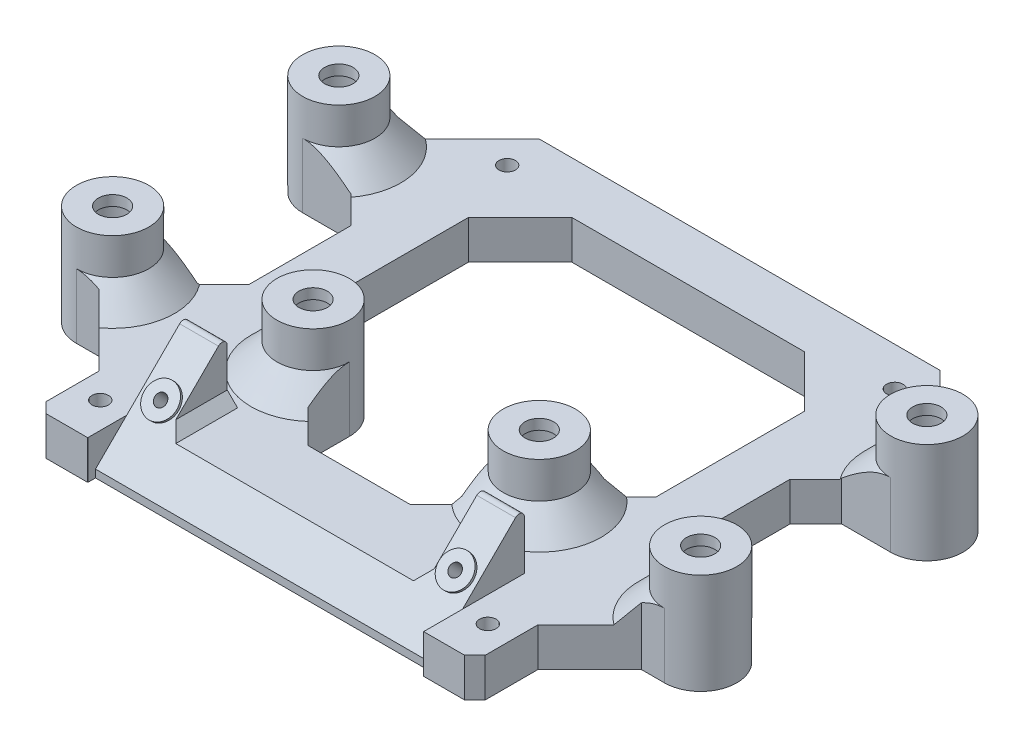
SolidWorks part; units mm, degrees
ref_plane "正面" through (0, 0, 0) normal (0, 0, 1) x (1, 0, 0)
ref_plane "平面" through (0, 0, 0) normal (0, 1, 0) x (1, 0, 0)
ref_plane "右側面" through (0, 0, 0) normal (1, 0, 0) x (0, 0, -1)
sketch "ｽｹｯﾁ1" plane through (0, 0, 0) normal (0, 1, 0) x (1, 0, 0)
  line L0 (42.4208, -126.095) -> (42.4208, 32.495) construction
  line L1 (42.4208, 32.495) -> (32.4208, 32.495) construction
  line L2 (32.4208, 32.495) -> (32.4208, -126.095) construction
  line L3 (32.4208, -126.095) -> (42.4208, -126.095) construction
  line L4 (-32.5792, -126.1) -> (-32.5792, 32.49) construction
  line L5 (-32.5792, 32.49) -> (-42.5792, 32.49) construction
  line L6 (-42.5792, 32.49) -> (-42.5792, -126.1) construction
  line L7 (-42.5792, -126.1) -> (-32.5792, -126.1) construction
  line L8 (42.4208, -126.095) -> (42.4208, -113.8873)
  line L9 (42.4208, 32.495) -> (32.4208, 32.495)
  line L10 (32.4208, -116.095) -> (32.4208, -126.095)
  line L11 (32.4208, -126.095) -> (42.4208, -126.095)
  line L12 (-32.5792, -126.1) -> (-32.5792, -116.095)
  line L13 (-32.5792, 32.49) -> (-42.5792, 32.49)
  line L14 (-42.5792, 32.49) -> (-42.5792, -36.1127)
  line L15 (-42.5792, -126.1) -> (-32.5792, -126.1)
  line L16 (42.4208, -36.1127) -> (42.4208, 32.495)
  line L17 (42.4208, 32.495) -> (32.4208, 32.495)
  line L18 (32.4208, -52.345) -> (32.4208, -126.095)
  line L19 (32.4208, -126.095) -> (42.4208, -126.095)
  line L20 (-32.5792, -126.1) -> (-32.5792, -52.345)
  line L21 (-32.5792, 32.49) -> (-42.5792, 32.49)
  line L22 (-42.5792, -113.8873) -> (-42.5792, -126.1)
  line L23 (-42.5792, -126.1) -> (-32.5792, -126.1)
  line L24 (0, 0) -> (0, -126.0975) construction
  line L25 (-14.8873, -93.1) -> (-14.8873, -106.095)
  line L26 (-32.5792, -126.1) -> (32.4208, -126.095) construction
  line L27 (-56.9, -89.8873) -> (-42.5792, -89.8873)
  line L28 (-56.9, -103.8873) -> (-52.5792, -103.8873)
  line L29 (-56.9, -60.1127) -> (-42.5792, -60.1127)
  line L30 (-56.9, -46.1127) -> (-52.5792, -46.1127)
  line L31 (14.8873, -93.1) -> (14.8873, -106.095)
  line L32 (-21.8873, -86.1) -> (-32.5792, -86.1)
  line L34 (21.8873, -86.1) -> (32.5792, -86.1)
  line L35 (56.9, -46.1127) -> (52.4208, -46.1127)
  line L36 (56.9, -60.1127) -> (42.5792, -60.1127)
  line L37 (56.9, -103.8873) -> (52.4208, -103.8873)
  line L38 (56.9, -89.8873) -> (42.5792, -89.8873)
  line L39 (-38.8115, -32.345) -> (38.6531, -32.345)
  line L40 (-42.5792, -36.1127) -> (-52.5792, -46.1127)
  line L41 (-52.5792, -103.8873) -> (-42.5792, -113.8873)
  line L42 (52.4208, -103.8873) -> (42.4208, -113.8873)
  line L43 (52.4208, -46.1127) -> (42.4208, -36.1127)
  line L45 (-32.5792, -106.095) -> (32.4208, -106.095)
  line L46 (-22.5792, -42.345) -> (22.4208, -42.345)
  line L47 (-32.5792, -52.345) -> (-22.5792, -42.345)
  line L48 (42.4208, -126.095) -> (42.4208, 32.495)
  line L49 (42.4208, 32.495) -> (32.4208, 32.495)
  line L50 (32.4208, 32.495) -> (32.4208, -126.095)
  line L51 (32.4208, -126.095) -> (42.4208, -126.095)
  line L52 (42.4208, -126.095) -> (42.4208, 32.495)
  line L53 (42.4208, 32.495) -> (32.4208, 32.495)
  line L54 (32.4208, 32.495) -> (32.4208, -126.095)
  line L55 (32.4208, -126.095) -> (42.4208, -126.095)
  line L56 (22.4208, -42.345) -> (32.4208, -52.345)
  line L57 (42.5792, -60.1127) -> (42.4208, -60.1127)
  line L58 (42.5792, -89.8873) -> (42.4208, -89.8873)
  line L59 (-42.5792, -36.1127) -> (-38.8115, -32.345)
  line L60 (42.4208, -36.1127) -> (38.6531, -32.345)
  line L61 (-32.5792, -126.1) -> (-32.5792, 32.49)
  line L62 (-32.5792, 32.49) -> (-42.5792, 32.49)
  line L63 (-42.5792, 32.49) -> (-42.5792, -126.1)
  line L64 (-42.5792, -126.1) -> (-32.5792, -126.1)
  line L65 (-32.5792, -126.1) -> (-32.5792, 32.49)
  line L66 (-32.5792, 32.49) -> (-42.5792, 32.49)
  line L67 (-42.5792, 32.49) -> (-42.5792, -126.1)
  line L68 (-42.5792, -126.1) -> (-32.5792, -126.1)
  line L69 (-32.5792, -106.095) -> (-32.5792, -116.095)
  line L70 (-32.5792, -116.095) -> (32.4208, -116.095)
  line L71 (32.4208, -106.095) -> (32.4208, -116.095)
  circle A0 centre (-21.8873, -93.1) radius 2.5 construction
  circle A1 centre (37.5, -27.5) radius 1.6
  circle A2 centre (37.5, -27.5) radius 1.6
  circle A3 centre (37.5, 27.5) radius 1.6
  circle A4 centre (37.5, 27.5) radius 1.6
  circle A5 centre (37.4208, -39.845) radius 1.6
  circle A6 centre (37.4208, -39.845) radius 1.6
  circle A7 centre (37.4208, -118.595) radius 1.6
  circle A8 centre (37.4208, -118.595) radius 1.6
  circle A9 centre (-37.5, -27.505) radius 1.6
  circle A10 centre (-37.5, -27.505) radius 1.6
  circle A11 centre (-37.5, 27.495) radius 1.6
  circle A12 centre (-37.5, 27.495) radius 1.6
  circle A13 centre (-37.5792, -39.85) radius 1.6
  circle A14 centre (-37.5792, -39.85) radius 1.6
  circle A15 centre (-37.5792, -118.6) radius 1.6
  circle A16 centre (-37.5792, -118.6) radius 1.6
  circle A17 centre (21.8873, -93.1) radius 2.5 construction
  circle A18 centre (56.9, -96.8873) radius 2.5 construction
  circle A19 centre (56.9, -53.1127) radius 2.5 construction
  circle A20 centre (-56.9, -96.8873) radius 2.5 construction
  circle A21 centre (-56.9, -53.1127) radius 2.5 construction
  circle A22 centre (-21.8873, -93.1) radius 2.5
  circle A23 centre (21.8873, -93.1) radius 2.5
  circle A24 centre (56.9, -96.8873) radius 2.5
  circle A25 centre (56.9, -53.1127) radius 2.5
  circle A26 centre (-56.9, -96.8873) radius 2.5
  circle A27 centre (-56.9, -53.1127) radius 2.5
  circle A28 centre (-21.8873, -93.1) radius 7
  circle A30 centre (-56.9, -53.1127) radius 7
  circle A31 centre (-56.9, -96.8873) radius 7
  circle A32 centre (21.8873, -93.1) radius 2.5
  circle A33 centre (21.8873, -93.1) radius 7
  circle A34 centre (56.9, -96.8873) radius 7
  circle A35 centre (56.9, -53.1127) radius 7
  circle A36 centre (56.9, -53.1127) radius 2.5
  circle A37 centre (56.9, -96.8873) radius 2.5
  point P62 (-42.5792, -103.8873)
  point P66 (-42.5792, -46.1127)
  point P97 (42.4208, -103.8873)
  point P99 (42.4208, -46.1127)
  point P110 (-32.5792, -42.345)
  point P111 (32.4208, -42.345)
  dimension "D9" = 14
  dimension "D10" = 14
  dimension "D21" = 14
  dimension "D11" = 7.5
  dimension "D20" = 10
  dimension "D19" = 10
  dimension "D13" = 10
  dimension "D1" = 0
  dimension "D2" = 0
  dimension "D3" = 0
  dimension "D4" = 0
  dimension "D5" = 0
  dimension "D6" = 0
  dimension "D7" = 0
  dimension "D8" = 0
  dimension "D12" = 0
  dimension "D18" = 0
extrude "ﾎﾞｽ - 押し出し1" add sketch "ｽｹｯﾁ1" along normal blind 7.5 contours A30 L29 L67 L40 L30 | A31 L28 L41 L67 L27 | L14 L67 L22 L15 L12 L20 L65 L39 A16 A14 | L39 L54 L18 L10 L11 L8 L52 L16 A8 A6 | L34 A33 L18 | A28 L32 L20 | A28 A22 | A31 A26 | A30 A27 | A35 A25 | L36 A35 L35 L43 L52 L57 | L65 L47 L46 L56 L54 L39 | L37 A34 L38 L58 L52 L42 | A34 A24 | A33 A23 | L20 L70 L18 L45 region at (37.3917, 0, 79.5741) region at (46.6794, 0, 99.8273) region at (-0.0792, 0, 111.095) region at (50.098, 0, 96.8873) region at (46.6794, 0, 50.1727) region at (23.654, 0, 105.8291) region at (-37.5502, 0, 79.5766) region at (-32.3122, 0, 96.0975) region at (50.098, 0, 53.1127) region at (-0.0792, 0, 38.4561) region at (26.697, 0, 88.2903) region at (-26.697, 0, 97.9097) region at (-46.7785, 0, 99.8648) region at (-63.702, 0, 96.8873) region at (-46.7785, 0, 50.1352) region at (-63.702, 0, 53.1127)
chamfer "面取り1" distance 10 angle 45 2 edges at (32.4208, 3.75, 116.095) (-32.5792, 3.75, 116.095)
chamfer "面取り2" distance 5 angle 45 2 edges at (14.8873, 3.75, 106.095) (-14.8873, 3.75, 106.095)
chamfer "面取り3" distance 5 angle 45 6 edges at (42.4208, 3.75, 89.8873) (42.4208, 3.75, 60.1127) (-42.5792, 3.75, 89.8873) (-42.5792, 3.75, 60.1127) (32.4208, 3.75, 86.1) (-32.5792, 3.75, 86.1)
chamfer "面取り4" distance 2 angle 45 2 edges at (42.4208, 3.75, 126.095) (-42.5792, 3.75, 126.1)
sketch "ｽｹｯﾁ2" plane through (0, 7.5, 0) normal (0, 1, 0) x (1, 0, 0)
  circle A0 centre (-56.9, -53.1127) radius 5.1
  circle A1 centre (-56.9, -96.8873) radius 5.1
  circle A2 centre (56.9, -53.1127) radius 5.1
  circle A3 centre (56.9, -96.8873) radius 5.1
  circle A4 centre (21.8873, -93.1) radius 5.1
  circle A5 centre (-21.8873, -93.1) radius 5.1
  dimension "D1" = 10.2
  dimension "D2" = 10.2
  dimension "D3" = 10.2
  dimension "D4" = 10.2
  dimension "D5" = 10.2
  dimension "D6" = 10.2
extrude "ｶｯﾄ - 押し出し1" cut sketch "ｽｹｯﾁ2" against normal blind 7.5
sketch "ｽｹｯﾁ3" plane through (0, 7.5, 0) normal (0, 1, 0) x (1, 0, 0)
  circle A0 centre (56.9, -96.8873) radius 5.1 construction
  circle A1 centre (21.8873, -93.1) radius 5.1 construction
  circle A2 centre (-21.8873, -93.1) radius 5.1 construction
  circle A3 centre (-56.9, -96.8873) radius 5.1 construction
  circle A4 centre (-56.9, -53.1127) radius 5.1 construction
  circle A5 centre (56.9, -53.1127) radius 5.1 construction
  circle A6 centre (56.9, -96.8873) radius 5.1
  circle A7 centre (21.8873, -93.1) radius 5.1
  circle A8 centre (-21.8873, -93.1) radius 5.1
  circle A9 centre (-56.9, -96.8873) radius 5.1
  circle A10 centre (-56.9, -53.1127) radius 5.1
  circle A11 centre (56.9, -53.1127) radius 5.1
  circle A12 centre (-56.9, -53.1127) radius 7
  circle A13 centre (-56.9, -96.8873) radius 7
  circle A14 centre (56.9, -53.1127) radius 7
  circle A15 centre (56.9, -96.8873) radius 7
  circle A16 centre (21.8873, -93.1) radius 7
  circle A17 centre (-21.8873, -93.1) radius 7
  dimension "D1" = 14
  dimension "D2" = 14
  dimension "D3" = 14
  dimension "D4" = 14
  dimension "D5" = 14
  dimension "D6" = 14
extrude "ﾎﾞｽ - 押し出し2" add sketch "ｽｹｯﾁ3" along normal blind 10
sketch "ｽｹｯﾁ4" plane through (0, 17.5, 0) normal (0, 1, 0) x (1, 0, 0)
  circle A0 centre (56.9, -53.1127) radius 7 construction
  circle A1 centre (56.9, -96.8873) radius 7 construction
  circle A2 centre (21.8873, -93.1) radius 7 construction
  circle A3 centre (-21.8873, -93.1) radius 7 construction
  circle A4 centre (-56.9, -96.8873) radius 7 construction
  circle A5 centre (-56.9, -53.1127) radius 7 construction
  circle A6 centre (56.9, -53.1127) radius 7
  circle A7 centre (56.9, -96.8873) radius 7
  circle A8 centre (21.8873, -93.1) radius 7
  circle A9 centre (-21.8873, -93.1) radius 7
  circle A10 centre (-56.9, -96.8873) radius 7
  circle A11 centre (-56.9, -53.1127) radius 7
  circle A12 centre (-56.9, -53.1127) radius 2.75
  circle A13 centre (-56.9, -96.8873) radius 2.75
  circle A14 centre (-21.8873, -93.1) radius 2.75
  circle A15 centre (21.8873, -93.1) radius 2.75
  circle A16 centre (56.9, -53.1127) radius 2.75
  circle A17 centre (56.9, -96.8873) radius 2.75
  dimension "D1" = 5.5
  dimension "D2" = 5.5
  dimension "D3" = 5.5
  dimension "D4" = 5.5
  dimension "D5" = 5.5
  dimension "D6" = 5.5
extrude "ﾎﾞｽ - 押し出し3" add sketch "ｽｹｯﾁ4" along normal blind 2
chamfer "面取り5" distance 5 angle 45 6 edges at (49.9, 7.5, 53.1127) (49.9, 7.5, 96.8873) (26.837, 7.5, 98.0497) (-26.837, 7.5, 98.0497) (-49.9, 7.5, 96.8873) (-49.9, 7.5, 53.1127)
sketch "ｽｹｯﾁ5" plane through (0, 0, 0) normal (0, -1, 0) x (1, 0, 0)
  line L0 (-56.9, 96.8873) -> (-46.9, 96.8873) construction
  line L1 (-56.9, 99.9873) -> (-46.9, 99.9873)
  line L2 (-56.9, 93.7873) -> (-46.9, 93.7873)
  line L3 (-56.9, 53.1127) -> (-46.9, 53.1127) construction
  line L4 (-56.9, 56.2127) -> (-46.9, 56.2127)
  line L5 (-56.9, 50.0127) -> (-46.9, 50.0127)
  line L6 (-21.8873, 93.1) -> (-28.9584, 100.1711) construction
  line L7 (-24.0793, 90.908) -> (-31.1504, 97.979)
  line L8 (-19.6953, 95.292) -> (-26.7663, 102.3631)
  line L9 (21.8873, 93.1) -> (28.9584, 100.1711) construction
  line L10 (19.6953, 95.292) -> (26.7663, 102.3631)
  line L11 (24.0793, 90.908) -> (31.1504, 97.979)
  line L12 (56.9, 96.8873) -> (46.9, 96.8873) construction
  line L13 (56.9, 93.7873) -> (46.9, 93.7873)
  line L14 (22.4208, 42.345) -> (32.4208, 52.345)
  line L15 (-22.5792, 42.345) -> (22.4208, 42.345)
  line L16 (-32.5792, 52.345) -> (-22.5792, 42.345)
  line L17 (-32.5792, 81.1) -> (-32.5792, 52.345)
  line L18 (-27.5792, 86.1) -> (-32.5792, 81.1)
  line L19 (-21.8873, 86.1) -> (-27.5792, 86.1)
  line L20 (-14.8873, 101.095) -> (-14.8873, 93.1)
  line L21 (-9.8873, 106.095) -> (-14.8873, 101.095)
  line L22 (9.8873, 106.095) -> (-9.8873, 106.095)
  line L23 (14.8873, 101.095) -> (9.8873, 106.095)
  line L24 (14.8873, 93.1) -> (14.8873, 101.095)
  line L25 (27.4208, 86.1) -> (21.8873, 86.1)
  line L26 (32.4208, 81.1) -> (27.4208, 86.1)
  line L27 (32.4208, 52.345) -> (32.4208, 81.1)
  line L28 (22.4208, 42.345) -> (32.4208, 52.345)
  line L29 (-22.5792, 42.345) -> (22.4208, 42.345)
  line L30 (-32.5792, 52.345) -> (-22.5792, 42.345)
  line L31 (-32.5792, 81.1) -> (-32.5792, 52.345)
  line L32 (-27.5792, 86.1) -> (-32.5792, 81.1)
  line L33 (-21.8873, 86.1) -> (-27.5792, 86.1)
  line L34 (-14.8873, 101.095) -> (-14.8873, 93.1)
  line L35 (-9.8873, 106.095) -> (-14.8873, 101.095)
  line L36 (9.8873, 106.095) -> (-9.8873, 106.095)
  line L37 (14.8873, 101.095) -> (9.8873, 106.095)
  line L38 (14.8873, 93.1) -> (14.8873, 101.095)
  line L39 (27.4208, 86.1) -> (21.8873, 86.1)
  line L40 (32.4208, 81.1) -> (27.4208, 86.1)
  line L41 (32.4208, 52.345) -> (32.4208, 81.1)
  line L42 (56.9, 99.9873) -> (46.9, 99.9873)
  line L43 (56.9, 53.1127) -> (46.9, 53.1127) construction
  line L44 (56.9, 50.0127) -> (46.9, 50.0127)
  line L45 (56.9, 56.2127) -> (46.9, 56.2127)
  arc A0 (-56.9, 99.9873) -> (-56.9, 93.7873) centre (-56.9, 96.8873) ccw
  circle A1 centre (-37.5792, 118.6) radius 1.6
  arc A2 (-21.8873, 86.1) -> (-14.8873, 93.1) centre (-21.8873, 93.1) ccw
  arc A3 (14.8873, 93.1) -> (21.8873, 86.1) centre (21.8873, 93.1) ccw
  arc A4 (-21.8873, 86.1) -> (-14.8873, 93.1) centre (-21.8873, 93.1) ccw
  arc A5 (14.8873, 93.1) -> (21.8873, 86.1) centre (21.8873, 93.1) ccw
  circle A6 centre (-37.5792, 118.6) radius 1.6
  circle A7 centre (-37.5792, 39.85) radius 1.6
  circle A8 centre (-37.5792, 39.85) radius 1.6
  circle A9 centre (37.4208, 118.595) radius 1.6
  circle A10 centre (37.4208, 118.595) radius 1.6
  circle A11 centre (37.4208, 39.845) radius 1.6
  circle A12 centre (37.4208, 39.845) radius 1.6
  circle A13 centre (-56.9, 53.1127) radius 5.1
  circle A14 centre (-56.9, 53.1127) radius 5.1
  circle A15 centre (-21.8873, 93.1) radius 5.1
  circle A16 centre (-21.8873, 93.1) radius 5.1
  circle A17 centre (-56.9, 96.8873) radius 5.1
  circle A18 centre (-56.9, 96.8873) radius 5.1
  circle A19 centre (56.9, 53.1127) radius 5.1
  circle A20 centre (56.9, 53.1127) radius 5.1
  circle A21 centre (56.9, 96.8873) radius 5.1
  circle A22 centre (56.9, 96.8873) radius 5.1
  circle A23 centre (21.8873, 93.1) radius 5.1
  circle A24 centre (21.8873, 93.1) radius 5.1
  arc A25 (-46.9, 93.7873) -> (-46.9, 99.9873) centre (-46.9, 96.8873) ccw
  circle A26 centre (-46.9, 96.8873) radius 1.4
  arc A27 (-56.9, 56.2127) -> (-56.9, 50.0127) centre (-56.9, 53.1127) ccw
  arc A28 (-46.9, 50.0127) -> (-46.9, 56.2127) centre (-46.9, 53.1127) ccw
  circle A29 centre (-46.9, 53.1127) radius 1.4
  arc A30 (-24.0793, 90.908) -> (-19.6953, 95.292) centre (-21.8873, 93.1) ccw
  arc A31 (-26.7663, 102.3631) -> (-31.1504, 97.979) centre (-28.9584, 100.1711) ccw
  arc A32 (19.6953, 95.292) -> (24.0793, 90.908) centre (21.8873, 93.1) ccw
  arc A33 (31.1504, 97.979) -> (26.7663, 102.3631) centre (28.9584, 100.1711) ccw
  arc A34 (56.9, 93.7873) -> (56.9, 99.9873) centre (56.9, 96.8873) ccw
  arc A35 (46.9, 99.9873) -> (46.9, 93.7873) centre (46.9, 96.8873) ccw
  arc A36 (56.9, 50.0127) -> (56.9, 56.2127) centre (56.9, 53.1127) ccw
  arc A37 (46.9, 56.2127) -> (46.9, 50.0127) centre (46.9, 53.1127) ccw
  circle A39 centre (-28.9584, 100.1711) radius 1.4
  circle A40 centre (28.9584, 100.1711) radius 1.4
  circle A41 centre (46.9, 96.8873) radius 1.4
  circle A42 centre (46.9, 53.1127) radius 1.4
  point P6 (-51.9, 96.8873)
  point P56 (-51.9, 53.1127)
  point P64 (-25.4228, 96.6355)
  point P70 (25.4228, 96.6355)
  point P76 (51.9, 96.8873)
  point P82 (51.9, 53.1127)
  dimension "D14" = 2.8
  dimension "D16" = 3.1
  dimension "D17" = 2.8
  dimension "D19" = 3.1
  dimension "D21" = 3.1
  dimension "D24" = 3.1
  dimension "D26" = 3.1
  dimension "D27" = 2.8
  dimension "D28" = 2.8
  dimension "D29" = 2.8
  dimension "D30" = 2.8
  dimension "D12" = 10
  dimension "D13" = 6.2
  dimension "D15" = 10
  dimension "D18" = 10
  dimension "D20" = 45
  dimension "D22" = 10
  dimension "D23" = 10
  dimension "D25" = 10
  dimension "D1" = 0
  dimension "D2" = 0
  dimension "D3" = 0
  dimension "D4" = 0
  dimension "D5" = 0
  dimension "D6" = 0
  dimension "D7" = 0
  dimension "D8" = 0
  dimension "D9" = 0
  dimension "D10" = 0
  dimension "D11" = 0
extrude "ｶｯﾄ - 押し出し2" cut sketch "ｽｹｯﾁ5" against normal blind 2.5 contours L2 A25 L1 A18 A26 | A26 | L7 A30 L8 A16 | L8 A31 L7 A16 A39 | A29 | L5 A28 L4 A14 A29 | L45 A37 L44 A20 A42 | A42 | A40 | L11 A33 L10 A24 A40 | A41 | L42 A35 L13 A22 A41 | A39 region at (-48.4792, 0, 96.8873) region at (-48.4792, 0, 53.1127) region at (-22.6926, 0, 93.9053) region at (-27.8417, 0, 99.0544) region at (27.8417, 0, 99.0544) region at (48.4792, 0, 96.8873) region at (48.4792, 0, 53.1127) region at (-46.9, 0, 96.8873) region at (-46.9, 0, 53.1127) region at (28.9584, 0, 100.1711) region at (46.9, 0, 96.8873) region at (46.9, 0, 53.1127)
sketch "ｽｹｯﾁ6" plane through (0, 2.5, 0) normal (0, -1, 0) x (1, 0, 0)
  line L2 (-46.9, 56.2127) -> (-56.9, 56.2127)
  line L3 (-56.9, 50.0127) -> (-46.9, 50.0127)
  line L4 (-46.9, 56.2127) -> (-56.9, 56.2127)
  line L5 (-56.9, 50.0127) -> (-46.9, 50.0127)
  line L6 (-46.9, 99.9873) -> (-56.9, 99.9873)
  line L7 (-56.9, 93.7873) -> (-46.9, 93.7873)
  line L8 (-46.9, 99.9873) -> (-56.9, 99.9873)
  line L9 (-56.9, 93.7873) -> (-46.9, 93.7873)
  line L10 (26.7663, 102.3631) -> (19.6953, 95.292)
  line L11 (24.0793, 90.908) -> (31.1504, 97.979)
  line L12 (26.7663, 102.3631) -> (19.6953, 95.292)
  line L13 (24.0793, 90.908) -> (31.1504, 97.979)
  line L14 (-9.8873, 106.095) -> (-14.8873, 101.095)
  line L15 (9.8873, 106.095) -> (-9.8873, 106.095)
  line L16 (14.8873, 101.095) -> (9.8873, 106.095)
  line L17 (14.8873, 93.1) -> (14.8873, 101.095)
  line L18 (27.4208, 86.1) -> (21.8873, 86.1)
  line L19 (32.4208, 81.1) -> (27.4208, 86.1)
  line L20 (32.4208, 52.345) -> (32.4208, 81.1)
  line L21 (22.4208, 42.345) -> (32.4208, 52.345)
  line L22 (-22.5792, 42.345) -> (22.4208, 42.345)
  line L23 (-32.5792, 52.345) -> (-22.5792, 42.345)
  line L24 (-32.5792, 81.1) -> (-32.5792, 52.345)
  line L25 (-27.5792, 86.1) -> (-32.5792, 81.1)
  line L26 (-21.8873, 86.1) -> (-27.5792, 86.1)
  line L27 (-14.8873, 101.095) -> (-14.8873, 93.1)
  line L28 (-9.8873, 106.095) -> (-14.8873, 101.095)
  line L29 (9.8873, 106.095) -> (-9.8873, 106.095)
  line L30 (14.8873, 101.095) -> (9.8873, 106.095)
  line L31 (14.8873, 93.1) -> (14.8873, 101.095)
  line L32 (27.4208, 86.1) -> (21.8873, 86.1)
  line L33 (32.4208, 81.1) -> (27.4208, 86.1)
  line L34 (32.4208, 52.345) -> (32.4208, 81.1)
  line L35 (22.4208, 42.345) -> (32.4208, 52.345)
  line L36 (-22.5792, 42.345) -> (22.4208, 42.345)
  line L37 (-32.5792, 52.345) -> (-22.5792, 42.345)
  line L38 (-32.5792, 81.1) -> (-32.5792, 52.345)
  line L39 (-27.5792, 86.1) -> (-32.5792, 81.1)
  line L40 (-21.8873, 86.1) -> (-27.5792, 86.1)
  line L41 (-14.8873, 101.095) -> (-14.8873, 93.1)
  line L42 (-31.1504, 97.979) -> (-24.0793, 90.908)
  line L43 (-19.6953, 95.292) -> (-26.7663, 102.3631)
  line L44 (-31.1504, 97.979) -> (-24.0793, 90.908)
  line L45 (-19.6953, 95.292) -> (-26.7663, 102.3631)
  line L46 (46.9, 50.0127) -> (56.9, 50.0127)
  line L47 (56.9, 56.2127) -> (46.9, 56.2127)
  line L48 (46.9, 50.0127) -> (56.9, 50.0127)
  line L49 (56.9, 56.2127) -> (46.9, 56.2127)
  line L50 (56.9, 99.9873) -> (46.9, 99.9873)
  line L51 (46.9, 93.7873) -> (56.9, 93.7873)
  line L52 (56.9, 99.9873) -> (46.9, 99.9873)
  line L53 (46.9, 93.7873) -> (56.9, 93.7873)
  circle A1 centre (-37.5792, 118.6) radius 1.6
  circle A2 centre (-37.5792, 118.6) radius 1.6
  circle A3 centre (37.4208, 39.845) radius 1.6
  circle A4 centre (37.4208, 39.845) radius 1.6
  circle A5 centre (37.4208, 118.595) radius 1.6
  circle A6 centre (37.4208, 118.595) radius 1.6
  circle A7 centre (-37.5792, 39.85) radius 1.6
  circle A8 centre (-37.5792, 39.85) radius 1.6
  circle A9 centre (56.9, 96.8873) radius 5.1
  arc A10 (14.8873, 93.1) -> (21.8873, 86.1) centre (21.8873, 93.1) ccw
  arc A11 (-21.8873, 86.1) -> (-14.8873, 93.1) centre (-21.8873, 93.1) ccw
  arc A12 (14.8873, 93.1) -> (21.8873, 86.1) centre (21.8873, 93.1) ccw
  arc A13 (-21.8873, 86.1) -> (-14.8873, 93.1) centre (-21.8873, 93.1) ccw
  circle A14 centre (56.9, 96.8873) radius 5.1
  circle A15 centre (56.9, 53.1127) radius 5.1
  circle A16 centre (56.9, 53.1127) radius 5.1
  circle A17 centre (-56.9, 96.8873) radius 5.1
  circle A18 centre (-56.9, 96.8873) radius 5.1
  circle A19 centre (-21.8873, 93.1) radius 5.1
  circle A20 centre (-21.8873, 93.1) radius 5.1
  circle A21 centre (-56.9, 53.1127) radius 5.1
  circle A22 centre (-56.9, 53.1127) radius 5.1
  circle A23 centre (-46.9, 53.1127) radius 1.4
  circle A24 centre (-46.9, 53.1127) radius 1.4
  circle A25 centre (-46.9, 96.8873) radius 1.4
  circle A26 centre (-46.9, 96.8873) radius 1.4
  circle A27 centre (21.8873, 93.1) radius 5.1
  circle A28 centre (21.8873, 93.1) radius 5.1
  circle A29 centre (46.9, 53.1127) radius 1.4
  arc A30 (-46.9, 50.0127) -> (-46.9, 56.2127) centre (-46.9, 53.1127) ccw
  arc A31 (-56.9, 56.2127) -> (-56.9, 50.0127) centre (-56.9, 53.1127) ccw
  arc A32 (-46.9, 50.0127) -> (-46.9, 56.2127) centre (-46.9, 53.1127) ccw
  arc A33 (-56.9, 56.2127) -> (-56.9, 50.0127) centre (-56.9, 53.1127) ccw
  arc A34 (-46.9, 93.7873) -> (-46.9, 99.9873) centre (-46.9, 96.8873) ccw
  arc A35 (-56.9, 99.9873) -> (-56.9, 93.7873) centre (-56.9, 96.8873) ccw
  arc A36 (-46.9, 93.7873) -> (-46.9, 99.9873) centre (-46.9, 96.8873) ccw
  arc A37 (-56.9, 99.9873) -> (-56.9, 93.7873) centre (-56.9, 96.8873) ccw
  arc A38 (31.1504, 97.979) -> (26.7663, 102.3631) centre (28.9584, 100.1711) ccw
  arc A39 (19.6953, 95.292) -> (24.0793, 90.908) centre (21.8873, 93.1) ccw
  arc A40 (31.1504, 97.979) -> (26.7663, 102.3631) centre (28.9584, 100.1711) ccw
  arc A41 (19.6953, 95.292) -> (24.0793, 90.908) centre (21.8873, 93.1) ccw
  arc A42 (-26.7663, 102.3631) -> (-31.1504, 97.979) centre (-28.9584, 100.1711) ccw
  arc A43 (-24.0793, 90.908) -> (-19.6953, 95.292) centre (-21.8873, 93.1) ccw
  arc A44 (-26.7663, 102.3631) -> (-31.1504, 97.979) centre (-28.9584, 100.1711) ccw
  arc A45 (-24.0793, 90.908) -> (-19.6953, 95.292) centre (-21.8873, 93.1) ccw
  circle A46 centre (46.9, 53.1127) radius 1.4
  circle A47 centre (46.9, 96.8873) radius 1.4
  circle A48 centre (46.9, 96.8873) radius 1.4
  circle A49 centre (28.9584, 100.1711) radius 1.4
  circle A50 centre (28.9584, 100.1711) radius 1.4
  circle A51 centre (-28.9584, 100.1711) radius 1.4
  circle A52 centre (-28.9584, 100.1711) radius 1.4
  arc A54 (46.9, 56.2127) -> (46.9, 50.0127) centre (46.9, 53.1127) ccw
  arc A55 (56.9, 50.0127) -> (56.9, 56.2127) centre (56.9, 53.1127) ccw
  arc A56 (46.9, 56.2127) -> (46.9, 50.0127) centre (46.9, 53.1127) ccw
  arc A57 (56.9, 50.0127) -> (56.9, 56.2127) centre (56.9, 53.1127) ccw
  arc A58 (46.9, 99.9873) -> (46.9, 93.7873) centre (46.9, 96.8873) ccw
  arc A59 (56.9, 93.7873) -> (56.9, 99.9873) centre (56.9, 96.8873) ccw
  arc A60 (46.9, 99.9873) -> (46.9, 93.7873) centre (46.9, 96.8873) ccw
  arc A61 (56.9, 93.7873) -> (56.9, 99.9873) centre (56.9, 96.8873) ccw
  dimension "D1" = 0
  dimension "D2" = 0
  dimension "D3" = 0
  dimension "D4" = 0
  dimension "D5" = 0
  dimension "D6" = 0
  dimension "D7" = 0
  dimension "D8" = 0
  dimension "D9" = 0
  dimension "D10" = 0
  dimension "D11" = 0
  dimension "D12" = 0
  dimension "D13" = 0
  dimension "D14" = 0
  dimension "D15" = 0
  dimension "D16" = 0
  dimension "D17" = 0
  dimension "D18" = 0
  dimension "D19" = 0
  dimension "D20" = 0
  dimension "D21" = 0
  dimension "D22" = 0
  dimension "D23" = 0
extrude "ｶｯﾄ - 押し出し3" cut sketch "ｽｹｯﾁ6" against normal blind 4 contours A26 | A52 | A50 | A48 | A46 | A24 region at (-46.9, 2.5, 53.1127) region at (-46.9, 2.5, 96.8873) region at (46.9, 2.5, 53.1127) region at (46.9, 2.5, 96.8873) region at (28.9584, 2.5, 100.1711) region at (-28.9584, 2.5, 100.1711)
sketch "ｽｹｯﾁ7" plane through (0, 0, 0) normal (0, 1, 0) x (1, 0, 0)
  line L0 (-32.5792, -126.1) -> (32.4208, -126.095) construction
  line L21 (42.4208, -65.1127) -> (47.2661, -60.2673)
  line L22 (49.7692, -43.4612) -> (38.6531, -32.345)
  line L23 (38.6531, -32.345) -> (-38.8115, -32.345)
  line L24 (-38.8115, -32.345) -> (-49.8607, -43.3942)
  line L25 (-47.334, -60.3579) -> (-42.5792, -65.1127)
  line L26 (-42.5792, -65.1127) -> (-42.5792, -84.8873)
  line L27 (-42.5792, -84.8873) -> (-47.334, -89.6421)
  line L28 (-49.8607, -106.6058) -> (-42.5792, -113.8873)
  line L29 (-42.5792, -113.8873) -> (-42.5792, -124.1)
  line L30 (-42.5792, -124.1) -> (-40.5792, -126.1)
  line L31 (-40.5792, -126.1) -> (-32.5792, -126.1)
  line L32 (-32.5792, -126.1) -> (-32.5792, -126.095)
  line L33 (-32.5792, -126.095) -> (-22.5792, -116.095)
  line L34 (-22.5792, -116.095) -> (22.4208, -116.095)
  line L35 (22.4208, -116.095) -> (32.4208, -126.095)
  line L36 (32.4208, -126.095) -> (40.4208, -126.095)
  line L37 (40.4208, -126.095) -> (42.4208, -124.095)
  line L38 (42.4208, -124.095) -> (42.4208, -113.8873)
  line L39 (42.4208, -113.8873) -> (49.7692, -106.5388)
  line L40 (47.2661, -89.7327) -> (42.4208, -84.8873)
  line L41 (42.4208, -84.8873) -> (42.4208, -65.1127)
  line L42 (42.4208, -65.1127) -> (47.2661, -60.2673) construction
  line L43 (49.7692, -43.4612) -> (38.6531, -32.345) construction
  line L44 (38.6531, -32.345) -> (-38.8115, -32.345) construction
  line L45 (-38.8115, -32.345) -> (-49.8607, -43.3942) construction
  line L46 (-47.334, -60.3579) -> (-42.5792, -65.1127) construction
  line L47 (-42.5792, -65.1127) -> (-42.5792, -84.8873) construction
  line L48 (-42.5792, -84.8873) -> (-47.334, -89.6421) construction
  line L49 (-49.8607, -106.6058) -> (-42.5792, -113.8873) construction
  line L50 (-42.5792, -113.8873) -> (-42.5792, -124.1) construction
  line L51 (-42.5792, -124.1) -> (-40.5792, -126.1) construction
  line L52 (-40.5792, -126.1) -> (-32.5792, -126.1) construction
  line L53 (-32.5792, -126.1) -> (-32.5792, -126.095) construction
  line L54 (-32.5792, -126.095) -> (-22.5792, -116.095) construction
  line L55 (-22.5792, -116.095) -> (22.4208, -116.095) construction
  line L56 (22.4208, -116.095) -> (32.4208, -126.095) construction
  line L57 (32.4208, -126.095) -> (40.4208, -126.095) construction
  line L58 (40.4208, -126.095) -> (42.4208, -124.095) construction
  line L59 (42.4208, -124.095) -> (42.4208, -113.8873) construction
  line L60 (42.4208, -113.8873) -> (49.7692, -106.5388) construction
  line L61 (47.2661, -89.7327) -> (42.4208, -84.8873) construction
  line L62 (42.4208, -84.8873) -> (42.4208, -65.1127) construction
  arc A4 (49.7692, -43.4612) -> (47.2661, -60.2673) centre (56.9, -53.1127) ccw
  arc A5 (-47.334, -60.3579) -> (-49.8607, -43.3942) centre (-56.9, -53.1127) ccw
  arc A6 (-49.8607, -106.6058) -> (-47.334, -89.6421) centre (-56.9, -96.8873) ccw
  arc A7 (47.2661, -89.7327) -> (49.7692, -106.5388) centre (56.9, -96.8873) ccw
  arc A8 (49.7692, -43.4612) -> (47.2661, -60.2673) centre (56.9, -53.1127) ccw construction
  arc A9 (-47.334, -60.3579) -> (-49.8607, -43.3942) centre (-56.9, -53.1127) ccw construction
  arc A10 (-49.8607, -106.6058) -> (-47.334, -89.6421) centre (-56.9, -96.8873) ccw construction
  arc A11 (47.2661, -89.7327) -> (49.7692, -106.5388) centre (56.9, -96.8873) ccw construction
  dimension "D1" = 0
sketch "ｽｹｯﾁ8" plane through (0, 0, 0) normal (1, 0, 0) x (0, 0, -1)
  line L0 (-46.1127, 12.5) -> (-46.1127, 11.2739)
  line L1 (-46.1127, 12.5) -> (-46.1127, 11.2739) construction
  line L2 (-46.1127, 11.2739) -> (-43.3942, 7.5)
  line L3 (-46.1127, 11.2739) -> (-43.3942, 7.5) construction
  line L4 (-43.3942, 7.5) -> (-32.345, 7.5)
  line L5 (-43.3942, 7.5) -> (-32.345, 7.5) construction
  line L6 (-32.345, 7.5) -> (-32.345, 0)
  line L7 (-32.345, 7.5) -> (-32.345, 0) construction
  line L8 (-32.345, 0) -> (-46.1127, 0)
  line L9 (-32.345, 0) -> (-46.1127, 0) construction
  line L10 (-46.1127, 0) -> (-60.1127, 0)
  line L11 (-46.1127, 0) -> (-60.1127, 0) construction
  line L12 (-60.1127, 0) -> (-65.1127, 0)
  line L13 (-60.1127, 0) -> (-65.1127, 0) construction
  line L14 (-65.1127, 0) -> (-84.8873, 0)
  line L15 (-65.1127, 0) -> (-84.8873, 0) construction
  line L16 (-84.8873, 0) -> (-89.8873, 0)
  line L17 (-84.8873, 0) -> (-89.8873, 0) construction
  line L18 (-89.8873, 0) -> (-103.8873, 0)
  line L19 (-89.8873, 0) -> (-103.8873, 0) construction
  line L20 (-103.8873, 0) -> (-113.8873, 0)
  line L21 (-103.8873, 0) -> (-113.8873, 0) construction
  line L22 (-113.8873, 0) -> (-124.1, 0)
  line L23 (-113.8873, 0) -> (-124.1, 0) construction
  line L24 (-124.1, 0) -> (-126.1, 0)
  line L25 (-124.1, 0) -> (-126.1, 0) construction
  line L26 (-126.1, 0) -> (-126.1, 7.5)
  line L27 (-126.1, 0) -> (-126.1, 7.5) construction
  line L28 (-126.1, 7.5) -> (-124.1, 7.5)
  line L29 (-126.1, 7.5) -> (-124.1, 7.5) construction
  line L30 (-124.1, 7.5) -> (-113.8873, 7.5)
  line L31 (-124.1, 7.5) -> (-113.8873, 7.5) construction
  line L32 (-113.8873, 7.5) -> (-106.6058, 7.5)
  line L33 (-113.8873, 7.5) -> (-106.6058, 7.5) construction
  line L34 (-106.6058, 7.5) -> (-103.8873, 11.2739)
  line L35 (-106.6058, 7.5) -> (-103.8873, 11.2739) construction
  line L36 (-103.8873, 11.2739) -> (-103.8873, 12.5)
  line L37 (-103.8873, 11.2739) -> (-103.8873, 12.5) construction
  line L38 (-103.8873, 12.5) -> (-103.8873, 19.5)
  line L39 (-103.8873, 12.5) -> (-103.8873, 19.5) construction
  line L40 (-103.8873, 19.5) -> (-89.8873, 19.5)
  line L41 (-103.8873, 19.5) -> (-89.8873, 19.5) construction
  line L42 (-89.8873, 19.5) -> (-86.1, 19.5)
  line L43 (-89.8873, 19.5) -> (-86.1, 19.5) construction
  line L44 (-86.1, 19.5) -> (-86.1, 12.5)
  line L45 (-86.1, 19.5) -> (-86.1, 12.5) construction
  line L46 (-86.1, 12.5) -> (-86.1, 10.577)
  line L47 (-86.1, 12.5) -> (-86.1, 10.577) construction
  line L48 (-86.1, 10.577) -> (-83.9132, 7.5)
  line L49 (-86.1, 10.577) -> (-83.9132, 7.5) construction
  line L50 (-83.9132, 7.5) -> (-81.1, 7.5)
  line L51 (-83.9132, 7.5) -> (-81.1, 7.5) construction
  line L52 (-81.1, 7.5) -> (-60.3579, 7.5)
  line L53 (-81.1, 7.5) -> (-60.3579, 7.5) construction
  line L54 (-60.3579, 7.5) -> (-60.1127, 7.8434)
  line L55 (-60.3579, 7.5) -> (-60.1127, 7.8434) construction
  line L56 (-60.1127, 7.8434) -> (-60.1127, 12.5)
  line L57 (-60.1127, 7.8434) -> (-60.1127, 12.5) construction
  line L58 (-60.1127, 12.5) -> (-60.1127, 19.5)
  line L59 (-60.1127, 12.5) -> (-60.1127, 19.5) construction
  line L60 (-60.1127, 19.5) -> (-46.1127, 19.5)
  line L61 (-60.1127, 19.5) -> (-46.1127, 19.5) construction
  line L62 (-46.1127, 19.5) -> (-46.1127, 12.5)
  line L63 (-46.1127, 19.5) -> (-46.1127, 12.5) construction
  line L64 (-126.1, 0) -> (-106.6058, 19.3965) construction
  line L69 (-116.095, 7.5) -> (-126.095, 7.5)
  line L70 (-126.095, 7.5) -> (-126.095, 0)
  line L71 (-126.095, 0) -> (-116.095, 0)
  line L72 (-116.095, 0) -> (-116.095, 7.5)
  line L73 (-116.095, 7.5) -> (-126.095, 7.5)
  line L74 (-126.095, 7.5) -> (-126.095, 0)
  line L75 (-126.095, 0) -> (-116.095, 0)
  line L76 (-116.095, 0) -> (-116.095, 7.5)
  dimension "D1" = 27.5
  dimension "D2" = 0
extrude "ｶｯﾄ - 押し出し4" cut sketch "ｽｹｯﾁ8" against normal mid plane 65
sketch "ｽｹｯﾁ10" plane through (0, 0, 0) normal (1, 0, 0) x (0, 0, -1)
  line L0 (-126.1, 0) -> (-106.6058, 19.3965) construction
  line L1 (-126.1, 0) -> (-106.6058, 19.3965)
  line L2 (-126.1, 0) -> (-127.2638, 1.1697) construction
  line L3 (-127.2638, 1.1697) -> (-107.7696, 20.5662) construction
  line L12 (-107.7696, 20.5662) -> (-106.6058, 19.3965) construction
  line L13 (-106.6058, 19.3965) -> (-106.6058, 0)
  line L14 (-106.6058, 0) -> (-126.1, 0)
  line L15 (-124.6, 1.4925) -> (-124.6, 0)
  dimension "D1" = 1.65
  dimension "D2" = 1.5
extrude "ﾎﾞｽ - 押し出し4" add sketch "ｽｹｯﾁ10" along normal mid plane 65 contours L1 L15 L14 L13 region at (0, 6.5011, 113.0324)
sketch "ｽｹｯﾁ11" plane through (0, 0, 106.6058) normal (0, 0, -1) x (-1, 0, 0)
  line L1 (-25, 19.3965) -> (25, 19.3965)
  line L2 (-25, 19.3965) -> (-25, 7.5)
  line L3 (-25, 7.5) -> (25, 7.5)
  line L4 (-32.5, 7.5) -> (32.5, 7.5)
  line L5 (-32.5, 19.3965) -> (-32.5, 7.5)
  line L6 (32.5, 19.3965) -> (-32.5, 19.3965)
  line L7 (-32.5, 19.3965) -> (-32.5, 7.5)
  line L8 (-32.5, 7.5) -> (32.5, 7.5)
  line L10 (32.5, 19.3965) -> (-32.5, 19.3965)
  line L12 (25, 19.3965) -> (25, 7.5)
  line L16 (32.5, 7.5) -> (32.5, 19.3965)
  line L17 (32.5, 7.5) -> (32.5, 19.3965)
  line M7 (-32.5, 7.5) -> (32.5, 7.5)
  line M9 (32.5, 19.3965) -> (-32.5, 19.3965)
  dimension "D2" = 7.5
  dimension "D3" = 7.5
  dimension "D1" = 0
extrude "ｶｯﾄ - 押し出し5" cut sketch "ｽｹｯﾁ11" against normal blind 65 contours L12 L2 M9 M7 region at (0, 13.4483, 106.6058)
fillet "ﾌｨﾚｯﾄ1" radius 1 2 edges at (28.75, 19.3965, 106.6058) (-28.75, 19.3965, 106.6058)
chamfer "面取り6" distance 2 angle 45 2 edges at (25, 7.5, 112.584) (-25, 7.5, 112.584)
sketch "ｽｹｯﾁ12" plane through (0, 0, 0) normal (0, -1, 0) x (1, 0, 0)
  line L1 (-32.5, 124.6) -> (32.5, 124.6)
  line L2 (-32.5, 124.6) -> (-32.5, 123.6)
  line L3 (-32.5, 123.6) -> (32.5, 123.6)
  line L4 (32.5, 124.6) -> (32.5, 123.6)
  line L14 (32.5, 108.3111) -> (32.5, 118.5622)
  line L15 (25, 108.3111) -> (32.5, 108.3111)
  line L16 (25, 116.5522) -> (25, 108.3111)
  line L17 (23, 118.5622) -> (25, 116.5522)
  line L18 (-23, 118.5622) -> (23, 118.5622)
  line L19 (-25, 116.5522) -> (-23, 118.5622)
  line L20 (-25, 108.3111) -> (-25, 116.5522)
  line L21 (-32.5, 108.3111) -> (-25, 108.3111)
  line L22 (32.5, 108.3111) -> (32.5, 118.5622)
  line L23 (-32.5, 124.6) -> (-32.5, 118.5622)
  line L24 (-32.5, 118.5622) -> (-32.5, 108.3111)
  line L25 (-32.5, 118.5622) -> (-32.5, 108.3111)
  line L26 (32.5, 124.6) -> (-32.5, 124.6)
  line L27 (32.5, 118.5622) -> (32.5, 124.6)
  line L29 (25, 108.3111) -> (32.5, 108.3111)
  line L30 (25, 116.5522) -> (25, 108.3111)
  line L31 (23, 118.5622) -> (25, 116.5522)
  line L32 (-23, 118.5622) -> (23, 118.5622)
  line L33 (-25, 116.5522) -> (-23, 118.5622)
  line L34 (-25, 108.3111) -> (-25, 116.5522)
  line L35 (-32.5, 108.3111) -> (-25, 108.3111)
  line L37 (-32.5, 124.6) -> (-32.5, 118.5622)
  line L41 (32.5, 118.5622) -> (32.5, 124.6)
  line L44 (32.5, 124.6) -> (-32.5, 124.6)
  dimension "D2" = 1
  dimension "D1" = 0
sketch "ｽｹｯﾁ13" plane through (0, 63.0492, 62.7333) normal (0, 0.7089, 0.7053) x (1, 0, 0)
  circle A0 centre (28.5, -74.6449) radius 1.35 construction
  circle A1 centre (-28.5, -74.6449) radius 1.35 construction
  circle A2 centre (28.5, -74.6449) radius 1.35 construction
  circle A3 centre (-28.5, -74.6449) radius 1.35 construction
  circle A4 centre (-28.5, -74.6449) radius 1.15
  circle A5 centre (28.5, -74.6449) radius 1.15
  dimension "D1" = 2.3
  dimension "D2" = 2.3
extrude "ｶｯﾄ - 押し出し8" cut sketch "ｽｹｯﾁ13" against normal blind 5
sketch "ｽｹｯﾁ14" plane through (0, 63.0492, 62.7333) normal (0, 0.7089, 0.7053) x (1, 0, 0)
  circle A0 centre (28.5, -74.6449) radius 1.15 construction
  circle A1 centre (-28.5, -74.6449) radius 1.15 construction
  circle A2 centre (28.5, -74.6449) radius 1.15
  circle A3 centre (-28.5, -74.6449) radius 1.15
  circle A4 centre (-28.5, -74.6449) radius 3.15
  circle A5 centre (28.5, -74.6449) radius 3.15
  dimension "D1" = 2
extrude "ﾎﾞｽ - 押し出し5" add sketch "ｽｹｯﾁ14" along normal mid plane 1
